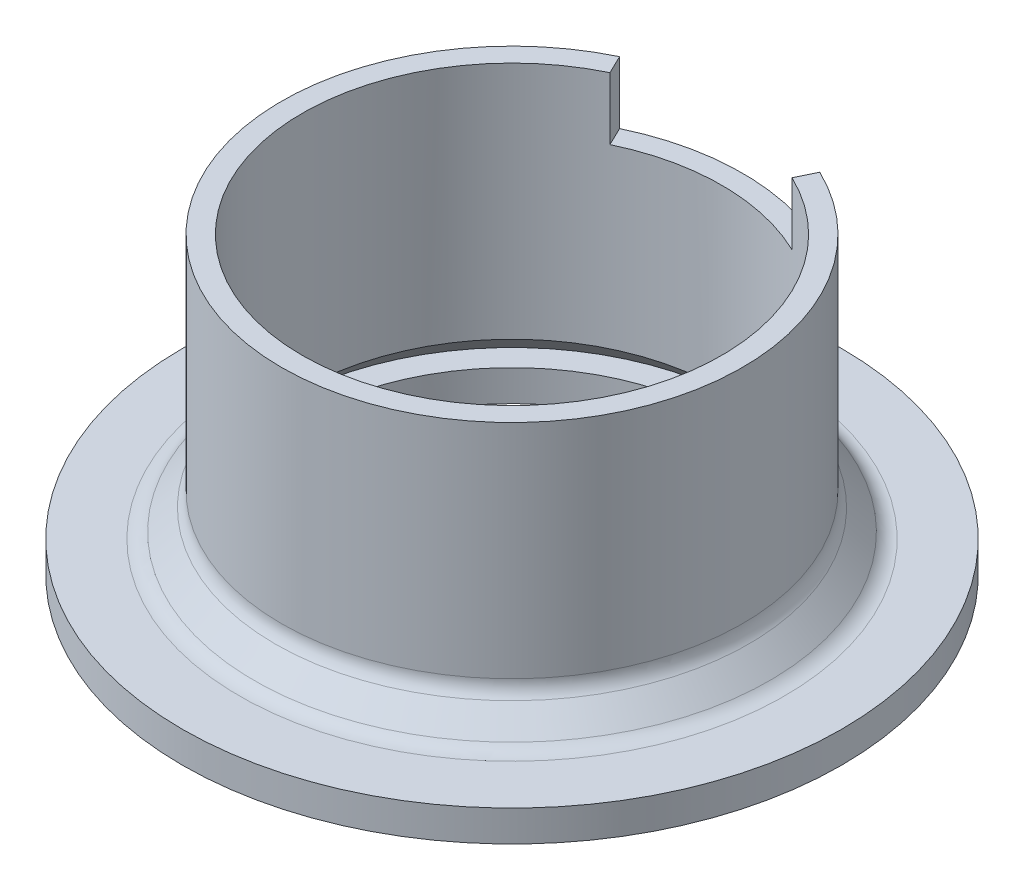
SolidWorks part; units mm, degrees
ref_plane "Front Plane" through (0, 0, 0) normal (0, 0, 1) x (1, 0, 0)
ref_plane "Top Plane" through (0, 0, 0) normal (0, 1, 0) x (1, 0, 0)
ref_plane "Right Plane" through (0, 0, 0) normal (1, 0, 0) x (0, 0, -1)
sketch3d "3DSketch1"
  line L0 (0, 25.4, 0) -> (0, 0, 0)
  line L1 (-22.2, 25.4, 0) -> (0, 25.4, 0)
  line L2 (-22.2, 25.4, 0) -> (-22.2, 3.2, 0)
  line L3 (-25.4, 0, 0) -> (-22.2, 3.2, 0)
  line L4 (0, 0, 0) -> (-25.4, 0, 0)
sketch "Sketch3" plane through (0, 0, 0) normal (0, 0, 1) x (1, 0, 0)
  line L1 (-22.2, 25.4) -> (-22.2, 3.2) construction
  line L2 (-25.4, 0) -> (-22.2, 3.2) construction
  line L4 (0, 25.4) -> (0, 0) construction
  line L5 (-22.2, 25.4) -> (-20.2, 25.4)
  line L6 (-22.2, 25.4) -> (-22.2, 3.2)
  line L7 (-25.4, 0) -> (-22.2, 3.2)
  line L8 (-20.2, 23.4) -> (-20.2, 2.3716) construction
  line L9 (0, 25.4) -> (0, 0)
  line L12 (-20.5716, 2) -> (-20.2, 2.3716) construction
  line L13 (-22.5716, 0) -> (-20.2, 2.3716)
  line L14 (-20.2, 25.4) -> (-20.2, 2.3716)
  line L15 (-2, 2) -> (-20.5716, 2) construction
  line L16 (-2, 23.4) -> (-2, 2) construction
  line L17 (-22.5716, 0) -> (-25.4, 0)
  line L18 (0, 0) -> (-25.4, 0) construction
  line L19 (-20.2, 23.4) -> (-2, 23.4) construction
  line L20 (-22.2, 25.4) -> (0, 25.4) construction
  dimension "D1" = 2
revolve "Revolve1" add sketch "Sketch3" angle 360 about L9 region at (-21.4103, 12.2091, 0)
sketch "Sketch4" plane through (0, 0, 0) normal (0, -1, 0) x (1, 0, 0)
  circle A0 centre (0, 0) radius 31.75
  circle A2 centre (0, 0) radius 20.2 construction
  circle A3 centre (0, 0) radius 20.2
extrude "Boss-Extrude1" add sketch "Sketch4" along normal blind 3
fillet "Fillet1" radius 2 1 edges at (0, 0, -25.4)
fillet "Fillet2" radius 2 1 edges at (0, 3.2, 22.2)
sketch "Sketch5" plane through (0, 0, 0) normal (0, 0, 1) x (1, 0, 0)
  line L0 (20.2, 0) -> (23.444, 0)
  line L1 (23.444, 1.439) -> (23.444, 0)
  line L2 (20.2, 4.6452) -> (20.2, 0)
  line L3 (23.444, 1.439) -> (20.2, 4.6452)
extrude "Boss-Extrude2" add sketch "Sketch5" along normal blind 1 and the other way blind 1
pattern_circular "CirPattern1" count 4 over 360 about axis through (0, 25.4, 0) along (0, 1, 0) of "Boss-Extrude2"
sketch "Sketch6" plane through (0, 25.4, 0) normal (0, 1, 0) x (1, 0, 0)
  line L1 (0, 20) -> (-13.8349, 20)
  line L2 (0, 20) -> (13.8349, 20)
  arc A0 (13.8349, 20) -> (-13.8349, 20) centre (0, 0) ccw
extrude "Cut-Extrude1" cut sketch "Sketch6" against normal blind 6
sketch "Sketch7" plane through (0, 25.4, 0) normal (0, 1, 0) x (1, 0, 0)
  line L0 (-9.6354, 20) -> (-2.8355, 20) construction
  line L1 (2.8355, 20) -> (9.6354, 20) construction
  line L2 (-9.6354, 20) -> (2.8355, 20)
  line L3 (2.8355, 20) -> (9.6354, 20)
  line L5 (-7.7532, 16.0932) -> (7.7532, 16.0932)
  line L6 (9.6354, 20) -> (7.7532, 16.0932)
  line L7 (-7.7532, 16.0932) -> (-9.6354, 20)
extrude "Cut-Extrude2" cut sketch "Sketch7" against normal blind 6
